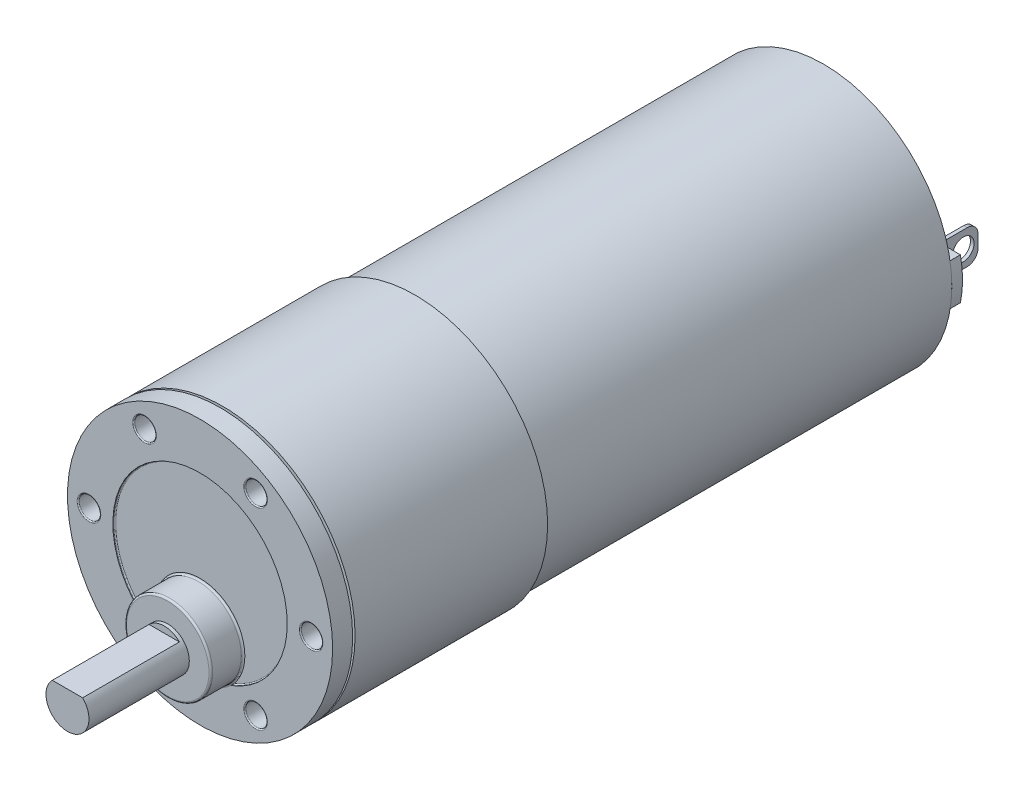
SolidWorks part; units mm, degrees
material "1.4305 (X8CrNiS18-9)"
ref_plane "Plan de face" through (0, 0, 0) normal (0, 0, 1) x (1, 0, 0)
ref_plane "Plan de dessus" through (0, 0, 0) normal (0, 1, 0) x (1, 0, 0)
ref_plane "Plan de droite" through (0, 0, 0) normal (1, 0, 0) x (0, 0, -1)
sketch "Esquisse1" plane through (0, 0, 0) normal (0, 0, 1) x (1, 0, 0)
  line L0 (183.3333, 550) -> (916.6667, 550) construction
  line L1 (277.0779, 228.3093) -> (314.0769, 228.5896) construction
  circle A2 centre (295.5635, 228.4536) radius 18.5
  dimension "D2" = 37
  dimension "D1" = 37
extrude "Boss.-Extru.1" add sketch "Esquisse1" against normal blind 30
sketch "Esquisse2" plane through (0, 0, 0) normal (0, 0, 1) x (1, 0, 0)
  line L0 (295.5635, 228.4536) -> (280.0635, 228.4536) construction
  circle A0 centre (295.5635, 228.4536) radius 15.5
  circle A1 centre (280.0635, 228.4536) radius 1.5
  circle A2 centre (287.8135, 241.877) radius 1.5
  circle A3 centre (303.3135, 241.877) radius 1.5
  circle A4 centre (311.0635, 228.4536) radius 1.5
  circle A5 centre (303.3135, 215.0302) radius 1.5
  circle A6 centre (287.8135, 215.0302) radius 1.5
  point P18 (295.5635, 228.4536)
  dimension "D1" = 6
extrude "Enlèv. mat.-Extru.1" cut sketch "Esquisse2" against normal blind 8 contours A4 | A5 | A1 | A2 | A3 | A6
sketch "Esquisse3" plane through (0, 0, 0) normal (0, 0, 1) x (1, 0, 0)
  line L0 (295.5635, 228.4536) -> (295.5635, 221.4536) construction
  circle A0 centre (295.5635, 221.4536) radius 6
  dimension "D1" = 7
extrude "Boss.-Extru.2" add sketch "Esquisse3" along normal blind 4.5
sketch "Esquisse4" plane through (0, 0, 4.5) normal (0, 0, 1) x (1, 0, 0)
  circle A0 centre (295.5635, 221.4536) radius 3
extrude "Boss.-Extru.3" add sketch "Esquisse4" along normal blind 14
fillet "Congé1" radius 0.25 2 edges at (301.5635, 221.4536, 0) (301.5635, 221.4536, 4.5)
sketch "Esquisse5" plane through (0, 0, 18.5) normal (0, 0, 1) x (1, 0, 0)
  line L0 (293.4458, 223.5786) -> (297.6811, 223.5786)
  circle A0 centre (295.5635, 221.4536) radius 3 construction
  arc A1 (293.4458, 223.5786) -> (297.6811, 223.5786) centre (295.5635, 221.4536) cw
extrude "Enlèv. mat.-Extru.2" cut sketch "Esquisse5" against normal blind 13.5
sketch "Esquisse6" plane through (0, 0, 0) normal (0, 0, 1) x (1, 0, 0)
  circle A0 centre (295.5635, 228.2853) radius 12.1671
extrude "Enlèv. mat.-Extru.3" cut sketch "Esquisse6" against normal blind 0.25
fillet "Congé2" radius 0.15 1 edges at (307.7306, 228.2853, -0.25)
fillet "Congé3" radius 0.15 6 edges at (281.5635, 228.4536, 0) (289.3135, 215.0302, 0) (304.8135, 215.0302, 0) (312.5635, 228.4536, 0) (289.3135, 241.877, 0) (304.8135, 241.877, 0)
sketch "Esquisse7" plane through (0, 0, -30) normal (0, 0, -1) x (-1, 0, 0)
  circle A0 centre (-295.5635, 228.4536) radius 17.9
extrude "Boss.-Extru.4" add sketch "Esquisse7" along normal blind 57
sketch "Esquisse8" plane through (0, 0, -87) normal (0, 0, -1) x (-1, 0, 0)
  circle A0 centre (-295.5635, 228.4536) radius 6.45
extrude "Boss.-Extru.5" add sketch "Esquisse8" along normal blind 4.9
fillet "Congé4" radius 3 1 edges at (289.1135, 228.4536, -91.9)
sketch "Esquisse9" plane through (0, 0, -87) normal (0, 0, -1) x (-1, 0, 0)
  line L0 (-313.4635, 228.4536) -> (-277.6635, 228.4536) construction
  line L1 (-277.6635, 228.4536) -> (-277.6635, 231.3536) construction
  line L2 (-277.6987, 228.4536) -> (-282.6981, 228.4536) construction
  line L3 (-282.6981, 225.5536) -> (-282.6981, 231.3536)
  line L4 (-282.6981, 231.3536) -> (-277.9673, 231.3536)
  line L5 (-282.6981, 225.5536) -> (-277.9673, 225.5536)
  line L6 (-295.5635, 246.3536) -> (-295.5635, 210.5536) construction
  line L7 (-308.4288, 225.5536) -> (-308.4288, 231.3536)
  line L8 (-308.4288, 225.5536) -> (-313.1596, 225.5536)
  line L9 (-308.4288, 231.3536) -> (-313.1596, 231.3536)
  circle A0 centre (-295.5635, 228.4536) radius 17.9 construction
  circle A1 centre (-295.5635, 228.4536) radius 17.9 construction
  arc A2 (-277.9673, 231.3536) -> (-277.9673, 225.5536) centre (-291.6539, 228.4536) cw
  arc A3 (-313.1596, 231.3536) -> (-313.1596, 225.5536) centre (-299.473, 228.4536) ccw
  dimension "D1" = 2.9
extrude "Boss.-Extru.6" add sketch "Esquisse9" along normal blind 1.5
sketch "Esquisse10" plane through (0, 0, -88.5) normal (0, 0, -1) x (-1, 0, 0)
  line L0 (-295.5635, 228.4536) -> (-309.5655, 228.4536) construction
  line L1 (-295.5635, 246.3536) -> (-295.5635, 210.5536) construction
  line L2 (-309.8155, 226.0929) -> (-309.3155, 226.0929)
  line L3 (-309.8155, 226.0929) -> (-309.8155, 230.8144)
  line L4 (-309.8155, 230.8144) -> (-309.3155, 230.8144)
  line L5 (-309.3155, 226.0929) -> (-309.3155, 230.8144)
  line L6 (-309.8155, 226.0929) -> (-309.3155, 230.8144) construction
  line L7 (-309.8155, 230.8144) -> (-309.3155, 226.0929) construction
  line L8 (-281.3114, 226.0929) -> (-281.8114, 226.0929)
  line L9 (-281.3114, 226.0929) -> (-281.3114, 230.8144)
  line L10 (-281.3114, 230.8144) -> (-281.8114, 230.8144)
  line L11 (-281.8114, 226.0929) -> (-281.8114, 230.8144)
  arc A0 (-277.6635, 228.4536) -> (-313.4635, 228.4536) centre (-295.5635, 228.4536) ccw construction
  arc A1 (-313.4635, 228.4536) -> (-277.6635, 228.4536) centre (-295.5635, 228.4536) ccw construction
  dimension "D1" = 0.5
extrude "Boss.-Extru.7" add sketch "Esquisse10" along normal blind 5.8
fillet "Congé5" radius 1.5 4 edges at (309.5655, 230.8144, -94.3) (281.5614, 230.8144, -94.3) (281.5614, 226.0929, -94.3) (309.5655, 226.0929, -94.3)
sketch "Esquisse11" plane through (309.8155, 0, 0) normal (1, 0, 0) x (0, 0, -1)
  circle A0 centre (92.2502, 228.4536) radius 1.5
  dimension "D1" = 3
extrude "Enlèv. mat.-Extru.4" cut sketch "Esquisse11" against normal blind 5.8
ref_axis "Axe1" through (275.0777, 228.4536, -92.2502) along (1, 0, 0)
sketch "Esquisse12" plane through (281.3114, 0, 0) normal (-1, 0, 0) x (0, 0, 1)
  circle A0 centre (-92.2502, 228.4536) radius 1.5
extrude "Enlèv. mat.-Extru.5" cut sketch "Esquisse12" against normal blind 5.8
ref_plane "Plan1" through (295, 0, 0) normal (1, 0, 0) x (0, 0, -1)
sketch "Esquisse13" plane through (295, 0, 0) normal (1, 0, 0) x (0, 0, -1)
  line L0 (30, 246.186) -> (30, 210.5536) construction
  line L3 (2.7958, 245.9863) -> (3.1328, 245.9863)
  line L4 (2.7958, 245.9863) -> (2.7958, 247.8563)
  line L5 (2.7958, 247.8563) -> (3.1328, 247.8563)
  line L6 (3.1328, 245.9863) -> (3.1328, 247.8563)
  line L7 (30, 210.5536) -> (30, 246.3536) construction
  line L8 (30, 209.9536) -> (30, 246.9536) construction
  line L9 (30, 210.5536) -> (30, 228.3347) construction
  line L10 (30, 228.3347) -> (-9.7066, 228.3347) construction
  point P12 (2.8897, 245.9863)
  point P13 (3.1328, 247.8563)
ref_axis "Axe2" through (295.5635, 228.4536, -30) along (0, 0, 1)
revolve "Enlèvement de matière-Révolution2" cut sketch "Esquisse13" angle 360 about L10
